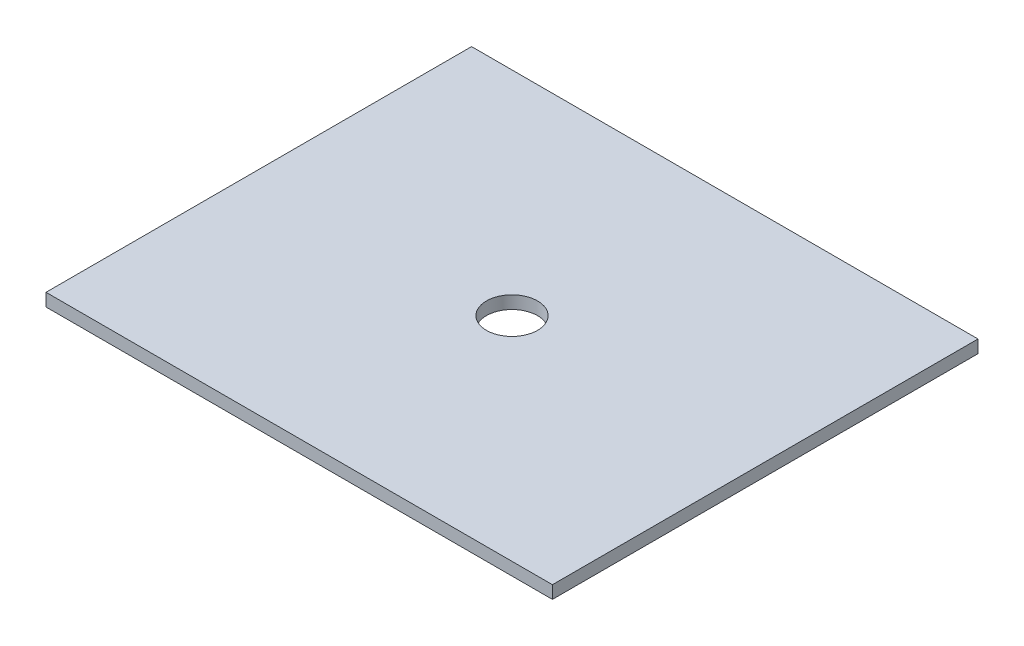
SolidWorks part; units mm, degrees
ref_plane "Front Plane" through (0, 0, 0) normal (0, 0, 1) x (1, 0, 0)
ref_plane "Top Plane" through (0, 0, 0) normal (0, 1, 0) x (1, 0, 0)
ref_plane "Right Plane" through (0, 0, 0) normal (1, 0, 0) x (0, 0, -1)
sketch "Sketch1" plane through (0, 0, 0) normal (0, 1, 0) x (1, 0, 0)
  line L6 (-29.75, 25) -> (29.75, 25)
  line L28 (-29.75, 25) -> (-29.75, -25)
  line L29 (-29.75, -25) -> (29.75, -25)
  line L30 (29.75, 25) -> (29.75, -25)
  line L31 (-29.75, 25) -> (29.75, -25) construction
  line L32 (-29.75, -25) -> (29.75, 25) construction
  circle A1 centre (0, 0) radius 3
  point P0 (0, 0)
  dimension "D3" = 6
  dimension "D1" = 59.5
  dimension "D2" = 50
extrude "Boss-Extrude1" add sketch "Sketch1" along normal blind 1.5
